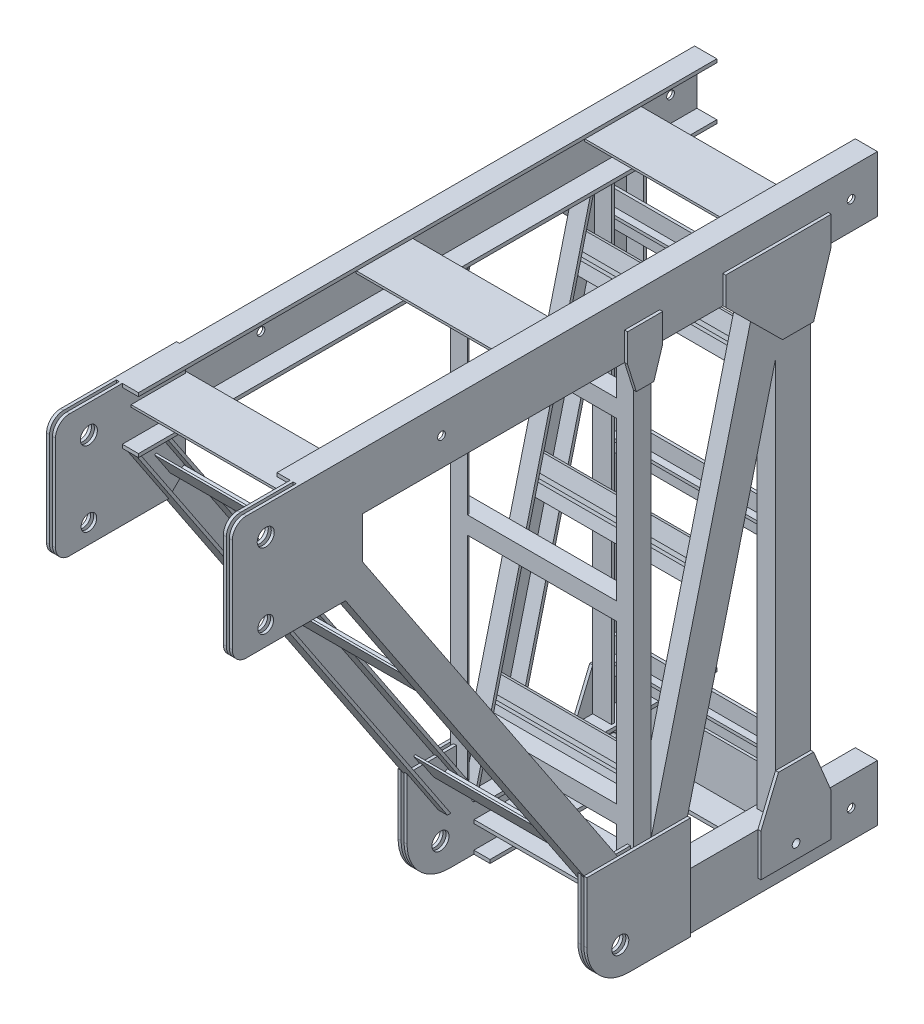
SolidWorks part; units mm, degrees
note: The reader was unsure of these and kept them because the rebuilt part matched: shared geometry of "草图38<2>".
ref_plane "前视基准面" through (0, 0, 0) normal (0, 0, 1) x (1, 0, 0)
ref_plane "上视基准面" through (0, 0, 0) normal (0, 1, 0) x (1, 0, 0)
ref_plane "右视基准面" through (0, 0, 0) normal (1, 0, 0) x (0, 0, -1)
sketch "草图2" plane through (0, 0, 0) normal (0, 0, 1) x (1, 0, 0)
  line L0 (0, 0) -> (0, 160)
  line L1 (0, 160) -> (63, 160)
  line L2 (63, 160) -> (63, 150)
  line L3 (63, 150) -> (6.5, 150)
  line L4 (6.5, 150) -> (6.5, 10)
  line L5 (6.5, 10) -> (63, 10)
  line L6 (63, 10) -> (63, 0)
  line L7 (63, 0) -> (0, 0)
  line L8 (457, 160) -> (520, 160)
  line L9 (520, 160) -> (520, 0)
  line L10 (520, 0) -> (457, 0)
  line L11 (457, 0) -> (457, 10)
  line L12 (457, 10) -> (513.5, 10)
  line L13 (513.5, 10) -> (513.5, 150)
  line L14 (513.5, 150) -> (457, 150)
  line L15 (457, 150) -> (457, 160)
  dimension "D1" = 160
  dimension "D2" = 10
  dimension "D3" = 6.5
  dimension "D4" = 63
  dimension "D5" = 520
extrude "拉伸1" add sketch "草图2" along normal blind 1835
pattern_linear "阵列(线性)2" count 2 spacing 1500 along (0, -1, 0) of "拉伸1"
sketch "草图4" plane through (0, -1340, 0) normal (0, 1, 0) x (1, 0, 0)
  line L0 (0, -1835) -> (0, 0) construction
  line L1 (520, -1835) -> (0, -1835)
  line L2 (520, -1835) -> (520, -835)
  line L3 (520, -835) -> (0, -835)
  line L4 (0, -1835) -> (0, -835)
  dimension "D1" = 1000
extrude "拉伸2" cut sketch "草图4" against normal blind 1000
sketch "草图5" plane through (0, 0, 0) normal (-1, 0, 0) x (0, 0, 1)
  line L0 (160, 95) -> (320, 95)
  line L1 (320, 95) -> (320, 88.5)
  line L2 (243.25, 88.5) -> (320, 88.5)
  line L3 (243.25, 88.5) -> (243.25, 48.5)
  line L4 (243.25, 48.5) -> (236.75, 48.5)
  line L5 (236.75, 48.5) -> (236.75, 88.5)
  line L6 (236.75, 88.5) -> (160, 88.5)
  line L7 (160, 88.5) -> (160, 95)
  line L8 (0, 160) -> (0, 0) construction
  point P10 (0, 80)
  dimension "D1" = 160
  dimension "D2" = 6.5
  dimension "D3" = 6.5
  dimension "D4" = 40
  dimension "D5" = 160
  dimension "D6" = 15
extrude "拉伸3" add sketch "草图5" against normal blind 520
sketch "草图8" plane through (0, 0, 0) normal (-1, 0, 0) x (0, 0, 1)
  line L0 (240, -1500) -> (240, 160) construction
  line L1 (1835, 160) -> (0, 160) construction
  line L2 (1835, 0) -> (0, 0) construction
  line L3 (190, 0) -> (290, 0)
  line L4 (190, 0) -> (190, -1340)
  line L5 (190, -1340) -> (290, -1340)
  line L6 (290, 0) -> (290, -1340)
  line L7 (835, -1340) -> (0, -1340) construction
  line L8 (835, -1500) -> (0, -1500) construction
  line L9 (0, -1340) -> (0, -1500) construction
  dimension "D1" = 50
  dimension "D2" = 50
  dimension "D3" = 240
extrude "拉伸7" add sketch "草图8" against normal blind 520 separate body
sketch "草图10" plane through (0, -1340, 0) normal (0, -1, 0) x (1, 0, 0)
  line L0 (466.7, 290) -> (466.7, 281.5)
  line L1 (520, 290) -> (0, 290) construction
  line L2 (466.7, 281.5) -> (514.7, 281.5)
  line L3 (514.7, 281.5) -> (514.7, 198.5)
  line L4 (514.7, 198.5) -> (466.7, 198.5)
  line L5 (466.7, 198.5) -> (466.7, 190)
  line L6 (520, 190) -> (0, 190) construction
  line L7 (53.3, 190) -> (53.3, 198.5)
  line L8 (53.3, 198.5) -> (5.3, 198.5)
  line L9 (5.3, 198.5) -> (5.3, 281.5)
  line L10 (53.3, 281.5) -> (53.3, 290)
  line L11 (53.3, 290) -> (466.7, 290)
  line L12 (5.3, 281.5) -> (53.3, 281.5)
  line L13 (53.3, 190) -> (466.7, 190)
  line L16 (0, 835) -> (0, 0) construction
  line L17 (520, 835) -> (520, 0) construction
  dimension "D1" = 5.3
  dimension "D2" = 5.3
  dimension "D3" = 8.5
  dimension "D4" = 48
extrude "拉伸9" cut sketch "草图10" against normal blind 1340
sketch "草图11" plane through (0, 0, 0) normal (-1, 0, 0) x (0, 0, 1)
  line L0 (1835, 160) -> (1835, 0) construction
  line L1 (1835, 80) -> (0, 80) construction
  line L2 (0, 160) -> (0, 0) construction
  circle A0 centre (1740, 80) radius 11
  dimension "D1" = 22
  dimension "D2" = 95
extrude "拉伸10" cut sketch "草图11" against normal through all
sketch "草图12" plane through (0, 0, 0) normal (-1, 0, 0) x (0, 0, 1)
  line L0 (645, -1420) -> (290, 0) construction
  line L1 (290, 0) -> (341.5388, 0)
  line L2 (1835, 0) -> (0, 0) construction
  line L3 (341.5388, 0) -> (676.5388, -1340)
  line L4 (676.5388, -1340) -> (573.4612, -1340)
  line L5 (573.4612, -1340) -> (290, -206.1553)
  line L6 (290, -1340) -> (290, 0) construction
  line L7 (290, -206.1553) -> (290, 0)
  line L8 (0, -1420) -> (835, -1420) construction
  line L9 (835, -1340) -> (0, -1340) construction
  line L10 (835, -1500) -> (835, -1340) construction
  line L11 (0, -1340) -> (0, -1500) construction
  dimension "D1" = 50
  dimension "D2" = 50
  dimension "D3" = 190
extrude "拉伸11" add sketch "草图12" against normal blind 48
pattern_linear "阵列(线性)3" count 2 spacing 472 along (1, 0, 0) of "拉伸11"
sketch "草图13" plane through (48, 0, 0) normal (1, 0, 0) x (0, 0, -1)
  line L0 (-332.7772, 0) -> (-290, 0)
  line L1 (-341.5388, 0) -> (-290, 0) construction
  line L2 (-290, 0) -> (-290, -171.1089)
  line L3 (-290, 0) -> (-290, -206.1553) construction
  line L4 (-290, -171.1089) -> (-582.2228, -1340)
  line L5 (-573.4612, -1340) -> (-676.5388, -1340) construction
  line L6 (-582.2228, -1340) -> (-667.7772, -1340)
  line L7 (-667.7772, -1340) -> (-332.7772, 0)
  line L8 (-676.5388, -1340) -> (-341.5388, 0) construction
  line L9 (-290, -206.1553) -> (-573.4612, -1340) construction
  dimension "D1" = 8.5
  dimension "D2" = 8.5
extrude "拉伸12" cut sketch "草图13" against normal blind 42.7
sketch "草图14" plane through (472, 0, 0) normal (-1, 0, 0) x (0, 0, 1)
  line L0 (290, -241.2017) -> (290, 0)
  line L1 (290, 0) -> (290, -206.1553) construction
  line L2 (290, 0) -> (332.7772, 0)
  line L3 (341.5388, 0) -> (290, 0) construction
  line L4 (332.7772, 0) -> (667.7772, -1340)
  line L5 (573.4612, -1340) -> (676.5388, -1340) construction
  line L6 (667.7772, -1340) -> (564.6996, -1340)
  line L7 (564.6996, -1340) -> (290, -241.2017)
  line L8 (676.5388, -1340) -> (341.5388, 0) construction
  line L9 (290, -206.1553) -> (573.4612, -1340) construction
  dimension "D1" = 8.5
  dimension "D2" = 8.5
extrude "拉伸13" cut sketch "草图14" against normal blind 42.7
sketch "草图15" plane through (0, 0, 0) normal (-1, 0, 0) x (0, 0, 1)
  line L0 (1645, 80) -> (645, -1420) construction
  line L1 (1591.6667, 0) -> (1543.5926, 0)
  line L2 (1835, 0) -> (341.5388, 0) construction
  line L3 (1543.5926, 0) -> (669.3717, -1311.3315)
  line L4 (676.5388, -1340) -> (341.5388, 0) construction
  line L5 (669.3717, -1311.3315) -> (676.5388, -1340)
  line L6 (676.5388, -1340) -> (746.4074, -1340)
  line L7 (835, -1340) -> (676.5388, -1340) construction
  line L8 (746.4074, -1340) -> (1639.7407, 0)
  line L9 (1639.7407, 0) -> (1591.6667, 0)
  line L10 (0, -1420) -> (835, -1420) construction
  line L11 (1740, 80) -> (0, 80) construction
  line L12 (0, 160) -> (0, 0) construction
  line L13 (0, -1340) -> (0, -1500) construction
  line L14 (835, -1500) -> (835, -1340) construction
  dimension "D1" = 40
  dimension "D2" = 40
  dimension "D3" = 190
  dimension "D4" = 95
extrude "拉伸14" add sketch "草图15" against normal blind 43
pattern_linear "阵列(线性)4" count 2 spacing 477 along (1, 0, 0) of "拉伸14"
sketch "草图16" plane through (477, 0, 0) normal (-1, 0, 0) x (0, 0, 1)
  line L0 (1553.2075, 0) -> (1630.1259, 0)
  line L1 (1639.7407, 0) -> (1543.5926, 0) construction
  line L2 (1630.1259, 0) -> (736.7925, -1340)
  line L3 (676.5388, -1340) -> (746.4074, -1340) construction
  line L4 (736.7925, -1340) -> (659.8741, -1340)
  line L5 (659.8741, -1340) -> (1553.2075, 0)
  line L6 (746.4074, -1340) -> (1639.7407, 0) construction
  line L7 (1543.5926, 0) -> (669.3717, -1311.3315) construction
  dimension "D1" = 8
  dimension "D2" = 8
extrude "拉伸15" cut sketch "草图16" against normal blind 38
sketch "草图17" plane through (43, 0, 0) normal (1, 0, 0) x (0, 0, -1)
  line L0 (-1630.1259, 0) -> (-1553.2075, 0)
  line L1 (-1639.7407, 0) -> (-1543.5926, 0) construction
  line L2 (-1553.2075, 0) -> (-659.8741, -1340)
  line L3 (-676.5388, -1340) -> (-746.4074, -1340) construction
  line L4 (-659.8741, -1340) -> (-736.7925, -1340)
  line L5 (-736.7925, -1340) -> (-1630.1259, 0)
  line L6 (-746.4074, -1340) -> (-1639.7407, 0) construction
  line L7 (-1543.5926, 0) -> (-669.3717, -1311.3315) construction
  dimension "D1" = 8
  dimension "D2" = 8
extrude "拉伸16" cut sketch "草图17" against normal blind 38
sketch "草图18" plane through (0, 0, 0) normal (-1, 0, 0) x (0, 0, 1)
  line L0 (669.3717, -1311.3315) -> (669.3717, 0.0067) construction
  line L1 (669.3717, -1311.3315) -> (341.5388, 0) construction
  line L2 (1543.5926, 0) -> (341.5388, 0) construction
  line L4 (644.3717, 0) -> (694.3717, 0)
  line L5 (644.3717, 0) -> (644.3717, -1211.3315)
  line L7 (694.3717, 0) -> (694.3717, -1273.8315)
  line L8 (1543.5926, 0) -> (669.3717, -1311.3315) construction
  line L9 (694.3717, -1273.8315) -> (669.3717, -1311.3315)
  line L10 (669.3717, -1311.3315) -> (644.3717, -1211.3315)
  dimension "D1" = 25
  dimension "D2" = 25
extrude "拉伸17" add sketch "草图18" against normal blind 520 separate body
sketch "草图19" plane through (0, 0, 0) normal (0, 1, 0) x (1, 0, 0)
  line L0 (457, -1835) -> (457, 0) construction
  line L1 (457, -644.3717) -> (63, -644.3717)
  line L2 (457, -644.3717) -> (457, -694.3717)
  line L3 (457, -694.3717) -> (63, -694.3717)
  line L4 (63, -644.3717) -> (63, -694.3717)
  line L5 (520, -644.3717) -> (0, -644.3717) construction
  line L6 (520, -694.3717) -> (0, -694.3717) construction
  line L7 (63, -1835) -> (63, 0) construction
extrude "拉伸18" cut sketch "草图19" against normal through all
sketch "草图20" plane through (457, 0, 0) normal (-1, 0, 0) x (0, 0, 1)
  line L0 (644.3717, 0) -> (694.3717, 0)
  line L1 (694.3717, 0) -> (694.3717, -1273.8315)
  line L2 (694.3717, -1273.8315) -> (669.3717, -1311.3315)
  line L3 (669.3717, -1311.3315) -> (644.3717, -1211.3315)
  line L4 (644.3717, -1211.3315) -> (669.3717, -1311.3315) construction
  line L5 (644.3717, -1211.3315) -> (644.3717, 0) construction
  line L6 (644.3717, -1211.3315) -> (644.3717, 0)
extrude "拉伸19" cut sketch "草图20" against normal blind 15
sketch "草图21" plane through (63, 0, 0) normal (1, 0, 0) x (0, 0, -1)
  line L0 (-694.3717, -1273.8315) -> (-669.3717, -1311.3315)
  line L1 (-669.3717, -1311.3315) -> (-644.3717, -1211.3315)
  line L2 (-644.3717, -1211.3315) -> (-644.3717, 0)
  line L3 (-1835, 0) -> (0, 0) construction
  line L4 (-644.3717, -1211.3315) -> (-644.3717, 0) construction
  line L5 (-644.3717, 0) -> (-694.3717, 0)
  line L6 (-644.3717, 0) -> (-694.3717, 0) construction
  line L7 (-694.3717, 0) -> (-694.3717, -1273.8315)
extrude "拉伸20" cut sketch "草图21" against normal blind 15
sketch "草图23" plane through (472, 0, 0) normal (-1, 0, 0) x (0, 0, 1)
  line L0 (689.3717, -1281.3315) -> (669.3717, -1311.3315)
  line L1 (669.3717, -1311.3315) -> (694.3717, -1273.8315) construction
  line L2 (669.3717, -1311.3315) -> (644.3717, -1211.3315)
  line L3 (644.3717, -1211.3315) -> (644.3717, 0)
  line L4 (694.3717, 0) -> (644.3717, 0) construction
  line L5 (644.3717, 0) -> (689.3717, 0)
  line L6 (689.3717, 0) -> (689.3717, -1281.3315)
  line L8 (694.3717, -1273.8315) -> (694.3717, 0) construction
  dimension "D1" = 5
extrude "拉伸21" cut sketch "草图23" against normal blind 45
sketch "草图24" plane through (48, 0, 0) normal (1, 0, 0) x (0, 0, -1)
  line L0 (-689.3717, -1281.3315) -> (-669.3717, -1311.3315)
  line L1 (-694.3717, -1273.8315) -> (-669.3717, -1311.3315) construction
  line L2 (-669.3717, -1311.3315) -> (-644.3717, -1211.3315)
  line L3 (-644.3717, -1211.3315) -> (-644.3717, 0)
  line L4 (-644.3717, 0) -> (-689.3717, 0)
  line L5 (-644.3717, 0) -> (-694.3717, 0) construction
  line L6 (-689.3717, 0) -> (-689.3717, -1281.3315)
  line L7 (-694.3717, 0) -> (-694.3717, -1273.8315) construction
  dimension "D1" = 5
extrude "拉伸22" cut sketch "草图24" against normal blind 45
pattern_linear "阵列(线性)6" count 3 spacing 650 along (0, 0, 1) of "拉伸3"
sketch "草图27" plane through (0, -1500, 0) normal (0, -1, 0) x (1, 0, 0)
  line L0 (0, 835) -> (0, 0) construction
  line L1 (0, 240) -> (520, 240)
  line L2 (0, 240) -> (0, 80)
  line L3 (0, 80) -> (520, 80)
  line L4 (520, 240) -> (520, 80)
  line L5 (520, 835) -> (520, 0) construction
  line L6 (0, 0) -> (63, 0) construction
  line L12 (0, 160) -> (520, 160) construction
  dimension "D1" = 160
  dimension "D2" = 80
extrude "拉伸24" add sketch "草图27" against normal blind 10
sketch "草图28" plane through (0, -1490, 0) normal (0, 1, 0) x (1, 0, 0)
  line L0 (513.5, -835) -> (513.5, 0) construction
  line L1 (513.5, -162.5) -> (6.5, -162.5)
  line L2 (513.5, -162.5) -> (513.5, -152.5)
  line L3 (513.5, -152.5) -> (6.5, -152.5)
  line L4 (6.5, -162.5) -> (6.5, -152.5)
  line L5 (6.5, -835) -> (6.5, 0) construction
  line L6 (63, -240) -> (63, -80) construction
  line L7 (457, -240) -> (457, -80) construction
  line L8 (63, -80) -> (457, -80) construction
  line L9 (457, -160) -> (63, -160) construction
  dimension "D1" = 10
  dimension "D2" = 5
extrude "拉伸25" add sketch "草图28" along normal blind 140
sketch "草图29" plane through (0, 0, 0) normal (-1, 0, 0) x (0, 0, 1)
  line L0 (240, -1340) -> (190, -1340) construction
  line L1 (240, -1340) -> (240, 160) construction
  line L2 (1835, 160) -> (0, 160) construction
  line L3 (231.5, -1165) -> (231.5, -1265)
  line L4 (231.5, -1265) -> (240, -1265)
  line L5 (240, -1265) -> (240, -1219.25)
  line L6 (240, -1219.25) -> (260, -1219.25)
  line L7 (260, -1219.25) -> (260, -1210.75)
  line L8 (260, -1210.75) -> (240, -1210.75)
  line L9 (240, -1210.75) -> (240, -1165)
  line L10 (240, -1165) -> (231.5, -1165)
  line L11 (190, 0) -> (190, -1340) construction
  line L12 (240, -1340) -> (290, -1340) construction
  dimension "D1" = 100
  dimension "D2" = 8.5
  dimension "D3" = 8.5
  dimension "D4" = 20
  dimension "D5" = 75
extrude "拉伸26" add sketch "草图29" against normal blind 520
pattern_linear "阵列(线性)9" count 3 spacing 550 along (0, 1, 0) of "拉伸26"
sketch "草图30" plane through (0, 0, 0) normal (-1, 0, 0) x (0, 0, 1)
  line L0 (665, -1500) -> (250, 160) construction
  line L1 (835, -1500) -> (0, -1500) construction
  line L2 (1835, 160) -> (0, 160) construction
  line L3 (290, -206.1553) -> (573.4612, -1340) construction
  line L5 (290, -206.1553) -> (338.5071, -194.0285) construction
  line L6 (338.5071, -194.0285) -> (387.0143, -181.9017) construction
  line L7 (669.3717, -1311.3315) -> (341.5388, 0) construction
  line L8 (313.8898, -130.6054) -> (338.1433, -227.6197)
  line L9 (338.1433, -227.6197) -> (346.3895, -225.5581)
  line L10 (346.3895, -225.5581) -> (335.2935, -181.1741)
  line L11 (335.2935, -181.1741) -> (354.6964, -176.3234)
  line L12 (354.6964, -176.3234) -> (352.6348, -168.0772)
  line L13 (352.6348, -168.0772) -> (333.232, -172.9279)
  line L14 (333.232, -172.9279) -> (322.136, -128.5439)
  line L15 (322.136, -128.5439) -> (313.8898, -130.6054)
  dimension "D1" = 100
  dimension "D2" = 8.5
  dimension "D3" = 8.5
  dimension "D4" = 20
  dimension "D5" = 120
extrude "拉伸27" add sketch "草图30" against normal blind 520
pattern_linear "阵列(线性)10" count 3 spacing 500 along (0, -0.9701, 0.2425) of "拉伸27"
sketch "草图31" plane through (520, 0, 0) normal (1, 0, 0) x (0, 0, -1)
  line L0 (-1548.9085, -59.6303) -> (-1504.5325, -126.1943)
  line L1 (-1548.9085, -59.6303) -> (-1553.0688, -62.4038)
  line L2 (-1504.5325, -126.1943) -> (-1508.6928, -128.9678)
  line L3 (-1553.0688, -62.4038) -> (-1508.6928, -128.9678)
  line L4 (-746.4074, -1340) -> (-713.1253, -1317.812) construction
  line L5 (-713.1253, -1317.812) -> (-679.8433, -1295.624) construction
  line L6 (-1698.3333, 160) -> (-713.1253, -1317.812) construction
  line L7 (-1835, 160) -> (0, 160) construction
  line L8 (-746.4074, -1340) -> (-1639.7407, 0) construction
  line L10 (-1543.5926, 0) -> (-669.3717, -1311.3315) construction
  line L11 (-1553.0688, -62.4038) -> (-1528.8006, -94.299) construction
  line L12 (-1548.9085, -59.6303) -> (-1508.6928, -128.9678) construction
  line L13 (-1528.8006, -94.299) -> (-1504.5325, -126.1943) construction
  dimension "D1" = 80
  dimension "D2" = 5
  dimension "D3" = 100
extrude "拉伸28" add sketch "草图31" against normal blind 520
sketch "草图32" plane through (0, -733.2286, 1099.843) normal (0, 0.5547, -0.8321) x (-1, 0, 0)
  line L1 (-457, 772.0645) -> (-63, 772.0645)
  line L2 (-457, 772.0645) -> (-457, 767.0645)
  line L3 (-457, 767.0645) -> (-63, 767.0645)
  line L4 (-63, 772.0645) -> (-63, 767.0645)
  line L7 (-457, 1151.0029) -> (-457, 133.128) construction
  line L9 (0, 769.5645) -> (-520, 769.5645) construction
  line L12 (-260, 769.5645) -> (-260, 809.5645) construction
  line L13 (-5, 809.5645) -> (-515, 809.5645) construction
  line L14 (-63, 1151.0029) -> (-63, 133.128) construction
  line L15 (-520, 1151.0029) -> (-520, 133.128) construction
  line L16 (0, 1151.0029) -> (0, 133.128) construction
  line L17 (-260, 769.5645) -> (-260, 729.5645) construction
  line L18 (-5, 729.5645) -> (-515, 729.5645) construction
  dimension "D1" = 2.5
  dimension "D2" = 2.5
extrude "拉伸29" add sketch "草图32" along normal blind 15
pattern_linear "阵列(线性)11" count 3 spacing 675 along (0, -0.8321, -0.5547) of "拉伸28", "拉伸29"
sketch "草图38" plane through (0, 0, 694.3717) normal (0, 0, 1) x (1, 0, 0)
  line L0 (0, -1273.8315) -> (0, 0) construction
  line L1 (0, -1123.8315) -> (520, -1123.8315)
  line L2 (0, -1123.8315) -> (0, -1173.8315)
  line L3 (0, -1173.8315) -> (520, -1173.8315)
  line L4 (520, -1123.8315) -> (520, -1173.8315)
  line L5 (520, -1273.8315) -> (520, 0) construction
  dimension "D1" = 50
  dimension "D2" = 100
extrude "拉伸36" add sketch "草图38" against normal blind 50
extrude "拉伸37" add sketch "草图38<2>" against normal blind 50
sketch "草图38<2>" plane through (0, 0, 694.3717) normal (0, 0, 1) x (1, 0, 0) same geometry as "草图38"
pattern_linear "阵列(线性)13" count 3 spacing 500 along (0, 1, 0) of "拉伸37"
sketch "草图39" plane through (0, 0, 644.3717) normal (0, 0, -1) x (-1, 0, 0)
  line L0 (-3, -1211.3315) -> (-3, -1173.8315) construction
  line L1 (-517, -1173.8315) -> (-3, -1173.8315)
  line L2 (-517, -1173.8315) -> (-517, -1128.8315)
  line L3 (-517, -1128.8315) -> (-3, -1128.8315)
  line L4 (-3, -1173.8315) -> (-3, -1128.8315)
  line L6 (-517, -673.8315) -> (-3, -673.8315)
  line L7 (-517, -673.8315) -> (-517, -628.8315)
  line L8 (-517, -628.8315) -> (-3, -628.8315)
  line L9 (-3, -673.8315) -> (-3, -628.8315)
  line L10 (-517, -173.8315) -> (-3, -173.8315)
  line L11 (-517, -173.8315) -> (-517, -128.8315)
  line L12 (-517, -128.8315) -> (-3, -128.8315)
  line L13 (-3, -173.8315) -> (-3, -128.8315)
  dimension "D1" = 45
extrude "拉伸38" cut sketch "草图39" against normal blind 45
sketch "草图40" plane through (520, 0, 0) normal (1, 0, 0) x (0, 0, -1)
  line L0 (-746.4074, -1340) -> (-1639.7407, 0) construction
  line L1 (-835, -1500) -> (-540.2389, -1500)
  line L2 (-835, -1500) -> (-835, -1207.111)
  line L3 (-835, -1207.111) -> (-540.2389, -1207.111)
  line L4 (-540.2389, -1500) -> (-540.2389, -1207.111)
  line L5 (-290, -206.1553) -> (-573.4612, -1340) construction
extrude "拉伸39" add sketch "草图40" along normal blind 8.5
pattern_linear "阵列(线性)15" count 2 spacing 17 along (-1, 0, 0) of "拉伸39"
pattern_linear "阵列(线性)16" count 2 spacing 511.5 along (-1, 0, 0) of "拉伸39", "阵列(线性)15"
sketch "草图41" plane through (0, 0, 835) normal (0, 0, 1) x (1, 0, 0)
  line L0 (63, -1500) -> (-8.5, -1500) construction
  line L1 (8.5, -1500) -> (0, -1500)
  line L2 (8.5, -1500) -> (8.5, -1340)
  line L3 (8.5, -1340) -> (0, -1340)
  line L4 (0, -1500) -> (0, -1340)
  line L5 (8.5, -1340) -> (0, -1340) construction
  line L6 (8.5, -1350) -> (8.5, -1490) construction
  line L7 (528.5, -1500) -> (457, -1500) construction
  line L8 (17, -1340) -> (503, -1340)
  line L9 (17, -1340) -> (17, -1500)
  line L10 (17, -1500) -> (503, -1500)
  line L11 (503, -1340) -> (503, -1500)
  line L12 (503, -1350) -> (503, -1490) construction
  line L13 (520, -1340) -> (511.5, -1340) construction
  line L14 (511.5, -1340) -> (520, -1340)
  line L15 (511.5, -1340) -> (511.5, -1500)
  line L16 (511.5, -1500) -> (520, -1500)
  line L17 (520, -1340) -> (520, -1500)
  line L18 (511.5, -1350) -> (511.5, -1490) construction
  line L19 (63, -1340) -> (17, -1340) construction
  dimension "D1" = 8.5
extrude "拉伸40" cut sketch "草图41" against normal blind 190
sketch "草图42" plane through (503, 0, 0) normal (-1, 0, 0) x (0, 0, 1)
  line L0 (540.2389, -1420) -> (1335, -1420) construction
  line L1 (484.3717, -1415) -> (644.3717, -1415)
  line L2 (484.3717, -1415) -> (484.3717, -1425)
  line L3 (484.3717, -1425) -> (644.3717, -1425)
  line L4 (644.3717, -1415) -> (644.3717, -1425)
  line L5 (540.2389, -1490) -> (540.2389, -1350) construction
  line L8 (644.3717, 0) -> (644.3717, -1207.111) construction
  dimension "D1" = 10
  dimension "D2" = 160
  dimension "D3" = 5
extrude "拉伸41" add sketch "草图42" along normal blind 503
fillet "圆角1" radius 120 4 edges at (524.25, -1500, 835) (-4.25, -1500, 835) (12.75, -1500, 835) (507.25, -1500, 835)
sketch "草图43" plane through (-8.5, 0, 0) normal (-1, 0, 0) x (0, 0, 1)
  line L0 (715, -1500) -> (540.2389, -1500) construction
  line L1 (835, -1207.111) -> (835, -1380) construction
  circle A0 centre (740, -1420) radius 24.25
  dimension "D1" = 48.5
  dimension "D2" = 80
  dimension "D3" = 95
extrude "拉伸42" cut sketch "草图43" against normal through all
sketch "草图44" plane through (0, 0, 0) normal (-1, 0, 0) x (0, 0, 1)
  line L1 (1835, 160) -> (1465, 160)
  line L2 (1835, 160) -> (1835, -190)
  line L3 (1835, -190) -> (1465, -190)
  line L4 (1465, 160) -> (1465, -190)
  line L5 (1543.5926, 0) -> (1610.1567, -44.376) construction
  line L6 (835, -1207.111) -> (1639.7407, 0) construction
  line L7 (1465, -190) -> (1576.8747, -22.188) construction
  dimension "D1" = 350
extrude "拉伸43" add sketch "草图44" along normal blind 8.5
pattern_linear "阵列(线性)17" count 2 spacing 17 along (1, 0, 0) of "拉伸43"
sketch "草图45" plane through (0, 0, 1835) normal (0, 0, 1) x (1, 0, 0)
  line L0 (63, 160) -> (-8.5, 160) construction
  line L1 (0, -190) -> (8.5, -190)
  line L2 (0, -190) -> (0, 160)
  line L3 (0, 160) -> (8.5, 160)
  line L4 (8.5, -190) -> (8.5, 160)
  line L5 (8.5, -190) -> (8.5, 0) construction
  line L6 (520, 160) -> (457, 160) construction
  line L7 (17, -190) -> (513.5, -190)
  line L8 (17, -190) -> (17, 160)
  line L9 (17, 160) -> (513.5, 160)
  line L10 (513.5, -190) -> (513.5, 160)
  line L11 (513.5, 150) -> (513.5, 10) construction
extrude "拉伸44" cut sketch "草图45" against normal blind 190
chamfer "倒角1" distance 50 angle 45 2 edges at (-4.25, -190, 1465) (12.75, -190, 1465)
sketch "草图46" plane through (-8.5, 0, 0) normal (-1, 0, 0) x (0, 0, 1)
  line L0 (1835, 160) -> (1465, 160) construction
  line L2 (1835, -190) -> (1835, 160) construction
  circle A0 centre (1740, 80) radius 24.25
  dimension "D1" = 48.5
  dimension "D2" = 80
  dimension "D3" = 95
extrude "拉伸45" cut sketch "草图46" against normal through all
sketch "草图47" plane through (0, 0, 0) normal (-1, 0, 0) x (0, 0, 1)
  line L0 (140, 80) -> (140, 0)
  line L1 (190, 0) -> (0, 0) construction
  line L2 (140, 0) -> (190, -160)
  line L3 (190, -160) -> (278.4612, -160)
  line L5 (278.4612, -160) -> (440, 0)
  line L6 (644.3717, 0) -> (341.5388, 0) construction
  line L7 (440, 0) -> (440, 80)
  line L8 (440, 80) -> (140, 80)
  line L9 (190, 0) -> (190, -1340) construction
  line L10 (190, 0) -> (190, -1340) construction
  line L11 (0, 80) -> (1465, 80) construction
  line L12 (0, 160) -> (0, 0) construction
  line L13 (1465, 160) -> (1465, 0) construction
  line L14 (190, 0) -> (190, -160) construction
  line L15 (290, -206.1553) -> (540.2389, -1207.111) construction
  line L17 (540.2389, -1500) -> (0, -1500) construction
  line L21 (140, -1460) -> (340, -1460)
  line L22 (340, -1460) -> (340, -1340)
  line L24 (540.2389, -1340) -> (290, -1340) construction
  line L26 (340, -1340) -> (290, -1220)
  line L27 (290, -1340) -> (290, -206.1553) construction
  line L29 (290, -1220) -> (190, -1220)
  line L30 (190, -1220) -> (140, -1340)
  line L31 (190, -1340) -> (0, -1340) construction
  line L32 (140, -1340) -> (140, -1460)
  line L33 (644.3717, 0) -> (694.3717, 0) construction
  line L34 (694.3717, 0) -> (694.3717, -1207.111) construction
  line L35 (669.3717, 0) -> (669.3717, -1207.111) construction
  line L36 (644.3717, -1207.111) -> (694.3717, -1207.111) construction
  line L37 (619.3717, 80) -> (719.3717, 80)
  line L38 (719.3717, 80) -> (719.3717, 0)
  line L39 (1465, 0) -> (694.3717, 0) construction
  line L40 (719.3717, 0) -> (694.3717, -80)
  line L41 (694.3717, -80) -> (644.3717, -80)
  line L42 (644.3717, 0) -> (644.3717, -1207.111) construction
  line L43 (644.3717, -80) -> (619.3717, 0)
  line L44 (619.3717, 0) -> (619.3717, 80)
  line L45 (619.3717, 80) -> (669.3717, 0) construction
  line L46 (719.3717, 80) -> (669.3717, 0) construction
  dimension "D1" = 300
  dimension "D2" = 50
  dimension "D3" = 120
  dimension "D4" = 200
  dimension "D5" = 40
  dimension "D6" = 100
  dimension "D7" = 80
extrude "拉伸46" add sketch "草图47" along normal blind 8.5
pattern_linear "阵列(线性)19" count 2 spacing 528.5 along (1, 0, 0) of "拉伸46"
pattern_linear "阵列(线性)20" count 2 spacing 520 along (1, 0, 0) of "拉伸43"
pattern_linear "阵列(线性)21" count 2 spacing 503 along (1, 0, 0) of "拉伸43"
sketch "草图49" plane through (520, 0, 0) normal (1, 0, 0) x (0, 0, -1)
  line L0 (-1835, 160) -> (0, 160) construction
  line L1 (-1835, -190) -> (-1835, 160) construction
  circle A0 centre (-1740, 80) radius 24.25
  circle A1 centre (-1740, -135) radius 22.25
  dimension "D1" = 48.5
  dimension "D2" = 44.5
  dimension "D3" = 80
  dimension "D4" = 215
  dimension "D5" = 95
  dimension "D6" = 95
extrude "拉伸48" cut sketch "草图49" against normal through all
fillet "圆角2" radius 40 8 edges at (515.75, -190, 1835) (498.75, -190, 1835) (515.75, 160, 1835) (498.75, 160, 1835) (12.75, -190, 1835) (-4.25, -190, 1835) (12.75, 160, 1835) (-4.25, 160, 1835)
sketch "草图50" plane through (-8.5, 0, 0) normal (-1, 0, 0) x (0, 0, 1)
  line L0 (1740, 80) -> (0, 80) construction
  line L1 (0, 160) -> (0, 0) construction
  line L2 (740, -1420) -> (0, -1420) construction
  line L3 (0, -1340) -> (0, -1500) construction
  circle A0 centre (1240, 80) radius 11
  circle A1 centre (240, -1420) radius 11
  circle A2 centre (75, 80) radius 11
  circle A3 centre (75, -1420) radius 11
  dimension "D1" = 22
  dimension "D6" = 22
  dimension "D2" = 500
  dimension "D3" = 500
  dimension "D4" = 75
  dimension "D5" = 75
extrude "拉伸49" cut sketch "草图50" against normal through all
